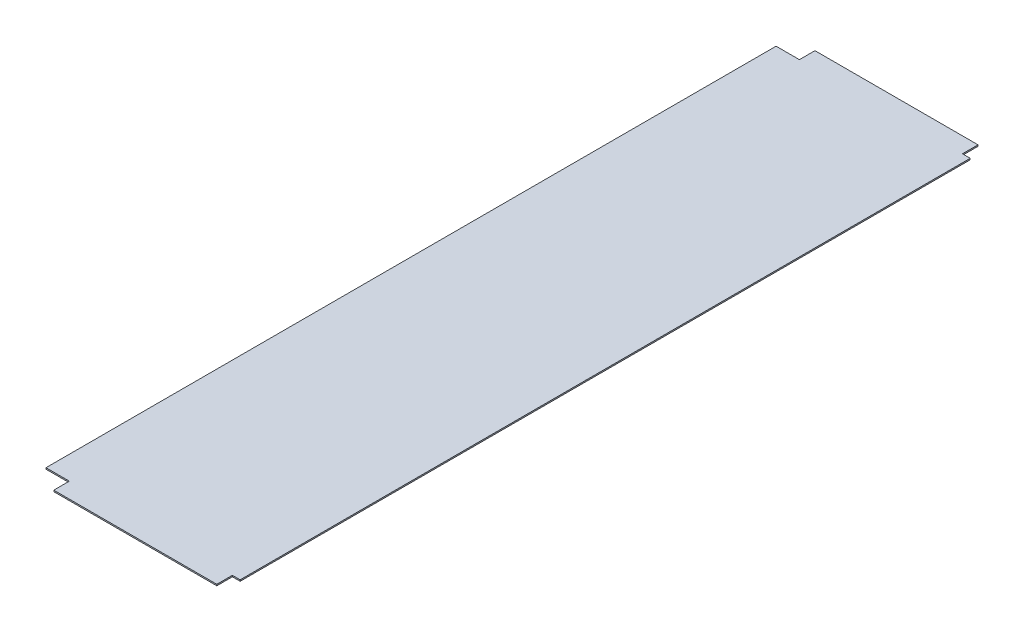
SolidWorks part; units mm, degrees
ref_plane "Front Plane" through (0, 0, 0) normal (0, 0, 1) x (1, 0, 0)
ref_plane "Top Plane" through (0, 0, 0) normal (0, 1, 0) x (1, 0, 0)
ref_plane "Right Plane" through (0, 0, 0) normal (1, 0, 0) x (0, 0, -1)
sketch "Sketch1" plane through (0, 0, 0) normal (0, 1, 0) x (1, 0, 0)
  line L0 (-110, 519) -> (-110, 499)
  line L1 (-110, -460) -> (99.7, -460)
  line L2 (-140, -440) -> (-140, 499)
  line L3 (-110, 519) -> (99.7, 519)
  line L4 (109.7, -440) -> (109.7, 499)
  line L5 (-134.1667, -440) -> (152.1572, 499) construction
  line L6 (-3618.7213, 499) -> (3190.8565, -440) construction
  line L7 (-110, 499) -> (-140, 499)
  line L8 (-213.9324, 29.5) -> (-140, 29.5) construction
  line L9 (99.7, 519) -> (99.7, 499)
  line L10 (99.7, 499) -> (109.7, 499)
  line L11 (-140, -440) -> (-110, -440)
  line L12 (-110, -440) -> (-110, -460)
  line L13 (109.7, -440) -> (99.7, -440)
  line L14 (99.7, -440) -> (99.7, -460)
  point P0 (0, 0)
  dimension "D1" = 249.7
  dimension "D2" = 10
  dimension "D3" = 30
  dimension "D4" = 20
  dimension "D5" = 10
  dimension "D6" = 20
  dimension "D7" = 20
  dimension "D8" = 30
  dimension "D9" = 979
base flange "Base-Flange1" sketch "Sketch1" thickness 1.7366 reverse thickness direction no parameters "D1"=0.7366
sketch "Bend-Lines1" [suppressed] plane through (0, 0, 0) normal (0, 1, 0) x (1, 0, 0)
sketch "Bounding-Box1" [suppressed] plane through (0, 0, 0) normal (0, 1, 0) x (1, 0, 0)
sheet metal parameters "Sheet-Metal1" thickness 1.7366 parameters "D1"=0.7366
flat pattern "Flat-Pattern1" [suppressed]
sketch "Bend-Lines2" plane through (0, 0, 0) normal (0, 1, 0) x (1, 0, 0)
sketch3d "Bounding-Box2" [suppressed]
  line L0 (-140, -460, 0) -> (-140, 519, 0) construction
  line L1 (109.7, -460, 0) -> (109.7, 519, 0) construction
  line L2 (-140, -460, 0) -> (109.7, -460, 0) construction
  line L3 (-140, 519, 0) -> (109.7, 519, 0) construction
